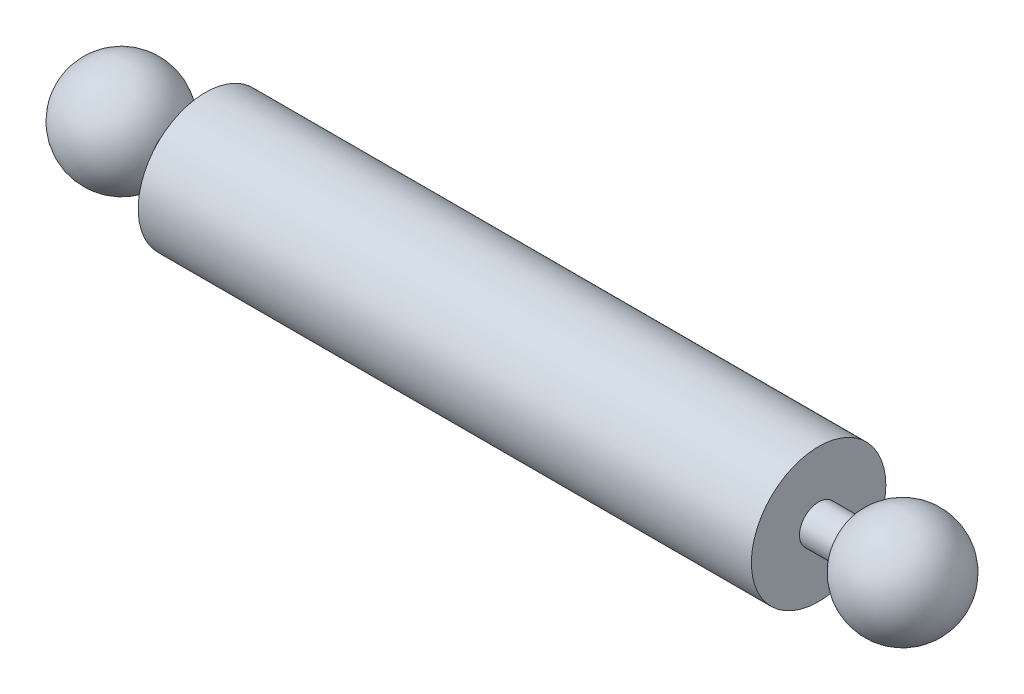
SolidWorks part; units mm, degrees
material "Chrome Stainless Steel"
ref_plane "Front Plane" through (0, 0, 0) normal (0, 0, 1) x (1, 0, 0)
ref_plane "Top Plane" through (0, 0, 0) normal (0, 1, 0) x (1, 0, 0)
ref_plane "Right Plane" through (0, 0, 0) normal (1, 0, 0) x (0, 0, -1)
sketch "Sketch1" plane through (0, 0, 0) normal (1, 0, 0) x (0, 0, -1)
  circle A0 centre (0, 0) radius 5.5689
  dimension "D1" = 11.1379
extrude "Boss-Extrude1" add sketch "Sketch1" along normal mid plane 50.8
sketch "Sketch2" plane through (-25.4, 0, 0) normal (-1, 0, 0) x (0, 0, 1)
  circle A0 centre (0, 0) radius 1.5875
  dimension "D1" = 3.175
extrude "Boss-Extrude2" add sketch "Sketch2" along normal blind 3.175
sketch "Sketch4" plane through (0, 0, 0) normal (0, 0, 1) x (1, 0, 0)
  line L0 (-36.7792, 0) -> (-27.94, 0)
  line L1 (-25.4, 0) -> (-27.94, 0)
  line L2 (-25.4, 5.5689) -> (-25.4, -5.5689) construction
  arc A0 (-27.94, 0) -> (-36.7792, 0) centre (-32.3596, 0) ccw
  dimension "D1" = 4.4196
  dimension "D2" = 2.54
revolve "Revolve1" add sketch "Sketch4" angle 360 about L0 region at (-32.3596, 1.8757, 0)
mirror "Mirror1" about plane through (0, 0, 0) normal (1, 0, 0) of "Revolve1", "Boss-Extrude2"
sketch "Sketch5" plane through (0, 0, 0) normal (0, 0, 1) x (1, 0, 0)
  line L0 (25.4, 0) -> (12.7, 0)
  line L1 (25.4, -1.5875) -> (25.4, 1.5875) construction
  circle A0 centre (12.7, 0) radius 1.5875
  dimension "D1" = 3.175
extrude "Cut-Extrude1" cut sketch "Sketch5" against normal blind 6.35 contours A0 region at (11.1574, 0, 0)
thread "Thread1" pitch 0.5292 method cut profile "Thread Profile2" start angle 0, offset 0, length 0, pitch 0.5292, diameter 3.175
ref_plane "Plane2" through (11.1125, 0, 0) normal (0, -1, 0) x (-1, 0, 0)
sketch "Thread Profile2" plane through (11.1125, 0, 0) normal (0, -1, 0) x (-1, 0, 0)
  line L0 (0, 0) -> (0, 0.5292) construction
  line L1 (0, 0) -> (0.2864, 0.1654)
  line L2 (0.2864, 0.1654) -> (0.2864, 0.2315)
  line L3 (0.2864, 0.2315) -> (0, 0.3969)
  line L4 (0.2864, 0.1984) -> (0, 0.1984) construction
  line L11 (0, 0) -> (0, 0.3969)
  point P2 (0, 0)
  dimension "Pitch" = 0.5292
  dimension "Profile_Angle" = 60
  dimension "Profile_Land" = 0.0661
  dimension "Profile_Height" = 0.2864
